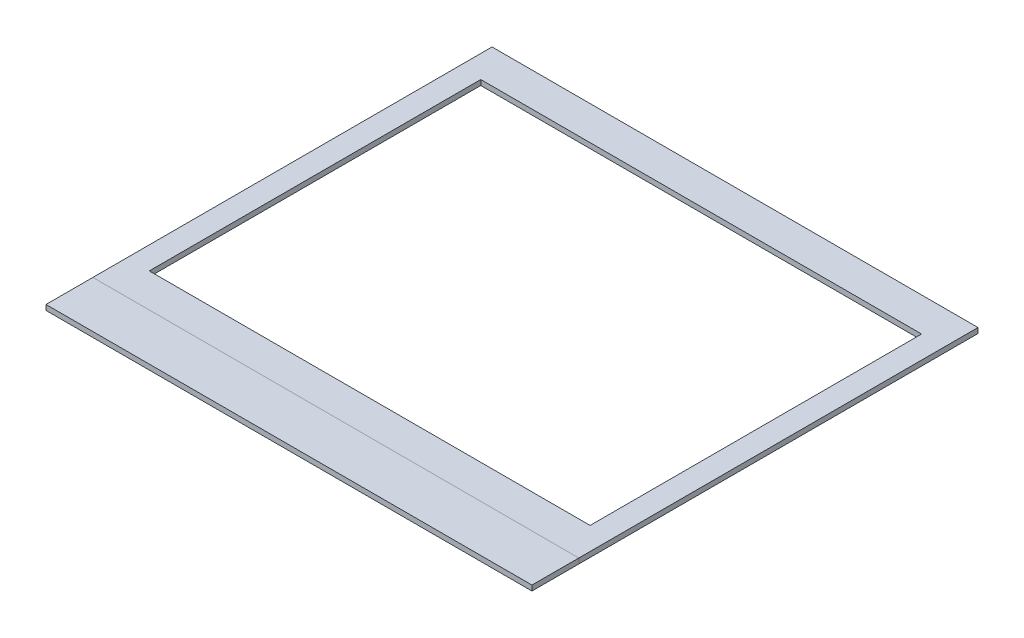
SolidWorks part; units mm, degrees
ref_plane "Front Plane" through (0, 0, 0) normal (0, 0, 1) x (1, 0, 0)
ref_plane "Top Plane" through (0, 0, 0) normal (0, 1, 0) x (1, 0, 0)
ref_plane "Right Plane" through (0, 0, 0) normal (1, 0, 0) x (0, 0, -1)
sketch "Sketch1" plane through (0, 0, 0) normal (0, 1, 0) x (1, 0, 0)
  line L0 (140, 230) -> (140, 210.5) construction
  line L1 (0, 0) -> (280, 0)
  line L2 (0, 0) -> (0, 230)
  line L3 (0, 230) -> (280, 230)
  line L4 (280, 0) -> (280, 230)
  line L5 (280, 210.5) -> (267, 210.5) construction
  line L6 (140, 0) -> (140, 19.5) construction
  line L7 (0, 19.5) -> (13, 19.5) construction
  line L9 (13, 19.5) -> (267, 19.5)
  line L10 (13, 19.5) -> (13, 210.5)
  line L11 (13, 210.5) -> (267, 210.5)
  line L12 (267, 19.5) -> (267, 210.5)
  dimension "D1" = 280
  dimension "D2" = 230
  dimension "D3" = 19.5
  dimension "D4" = 13
  dimension "D5" = 19.5
  dimension "D6" = 13
extrude "Boss-Extrude1" add sketch "Sketch1" along normal blind 3
sketch "Sketch4" plane through (0, 3, 0) normal (0, 1, 0) x (1, 0, 0)
  line L1 (0, 0) -> (280, 0)
  line L2 (0, 0) -> (0, -27)
  line L3 (0, -27) -> (280, -27)
  line L4 (280, 0) -> (280, -27)
  dimension "D1" = 27
extrude "Boss-Extrude2" add sketch "Sketch4" against normal blind 3 separate body
sketch "Sketch6" plane through (0, 0, 0) normal (0, -1, 0) x (1, 0, 0)
  line L0 (280, 27) -> (280, -230) construction
  line L2 (0, -230) -> (280, -230) construction
  dimension "D1" = 257
  dimension "D2" = 280
